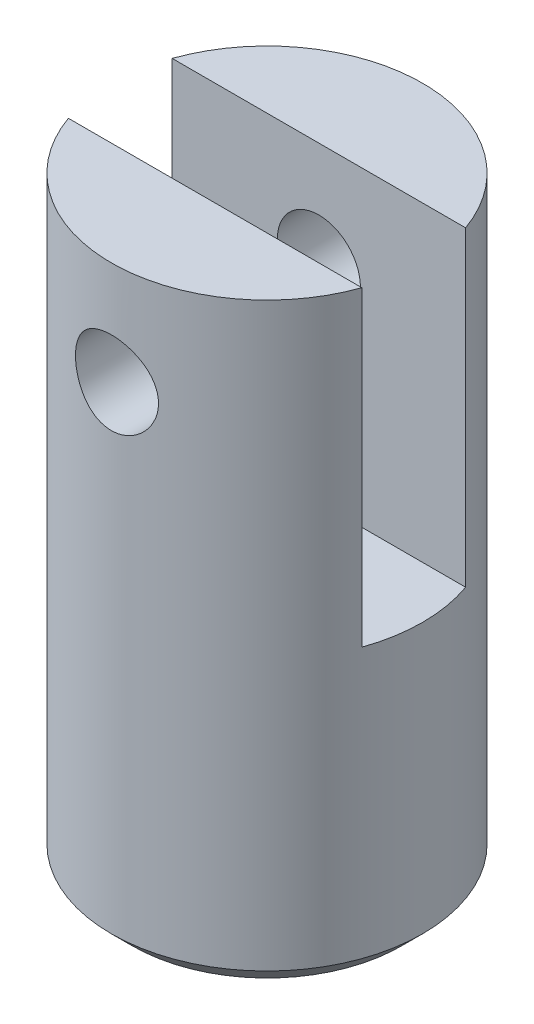
SolidWorks part; units mm, degrees
material "Aço cromo inoxidável"
ref_plane "Plano frontal" through (0, 0, 0) normal (0, 0, 1) x (1, 0, 0)
ref_plane "Plano superior" through (0, 0, 0) normal (0, 1, 0) x (1, 0, 0)
ref_plane "Plano direito" through (0, 0, 0) normal (1, 0, 0) x (0, 0, -1)
sketch "Esboço1" plane through (0, 0, 0) normal (0, 1, 0) x (1, 0, 0)
  circle A0 centre (0, 0) radius 7.5
  dimension "D1" = 15
extrude "Ressalto-extrusão1" add sketch "Esboço1" along normal mid plane 29
sketch "Esboço2" plane through (0, 0, 0) normal (1, 0, 0) x (0, 0, -1)
  line L0 (7.5, 14.5) -> (-7.5, 14.5) construction
  line L1 (-2.5, 14.5) -> (2.5, 14.5)
  line L2 (-2.5, 14.5) -> (-2.5, -0.5)
  line L3 (-2.5, -0.5) -> (2.5, -0.5)
  line L4 (2.5, 14.5) -> (2.5, -0.5)
  line L5 (0, -0.5) -> (0, 14.5) construction
  line L6 (-2.5, 7) -> (2.5, 7) construction
  point P204 (0, 7)
  dimension "D1" = 15
  dimension "D2" = 5
extrude "Corte-extrusão1" cut sketch "Esboço2" against normal through all both and the other way through all
sketch "Esboço3" plane through (0, 0, 0) normal (0, 0, 1) x (1, 0, 0)
  line L0 (0, 14.5) -> (0, 9.5) construction
  line L1 (7.0711, 14.5) -> (-7.0711, 14.5) construction
  circle A0 centre (0, 9.5) radius 2
  dimension "D2" = 4
  dimension "D1" = 5
extrude "Corte-extrusão2" cut sketch "Esboço3" against normal through all both and the other way through all
chamfer "Chanfro1" distance 1 angle 45 1 edges at (0, -14.5, 7.5)
